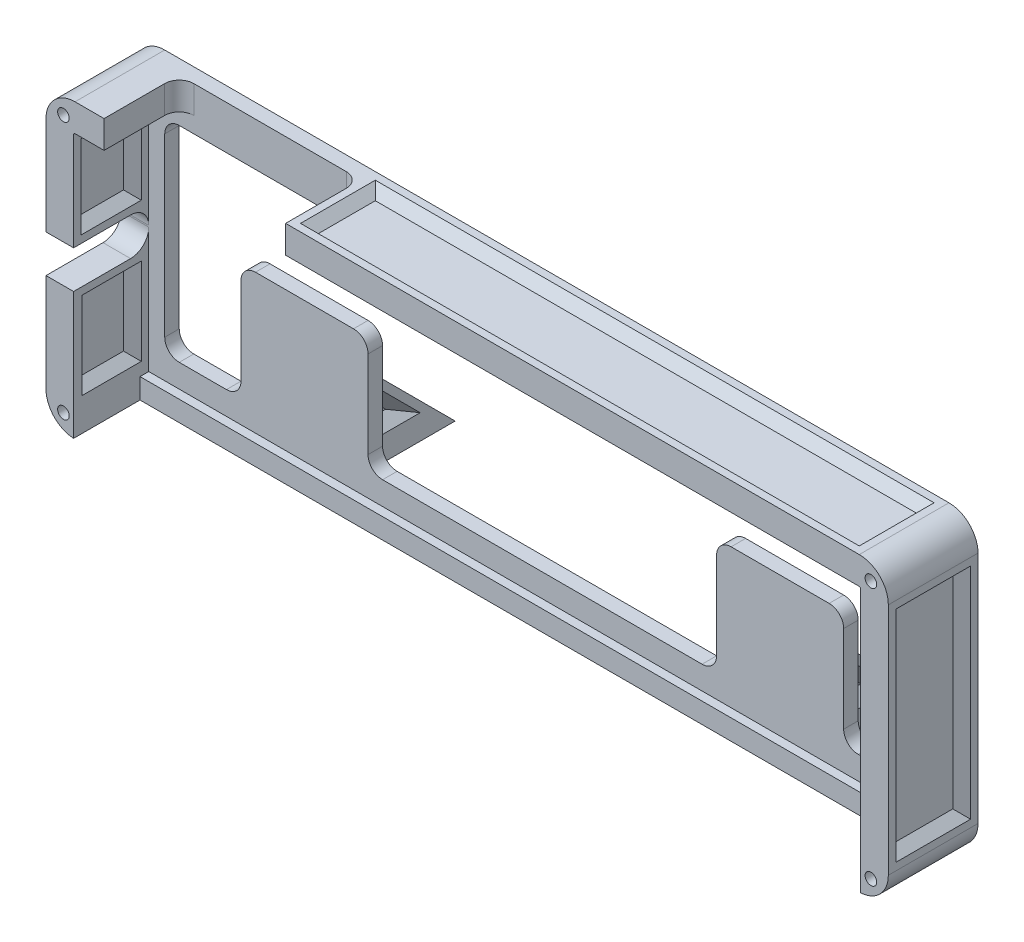
SolidWorks part; units mm, degrees
material "6061-T6 (SS)"
ref_plane "Front Plane" through (0, 0, 0) normal (0, 0, 1) x (1, 0, 0)
ref_plane "Top Plane" through (0, 0, 0) normal (0, 1, 0) x (1, 0, 0)
ref_plane "Right Plane" through (0, 0, 0) normal (1, 0, 0) x (0, 0, -1)
sketch "Sketch1" plane through (0, 0, 0) normal (0, 0, 1) x (1, 0, 0)
  line L0 (58, -16.125) -> (58, 16.125)
  line L1 (-54, -16.125) -> (54, -16.125) construction
  line L2 (-54, -16.125) -> (-54, 16.125) construction
  line L3 (-54, 16.125) -> (54, 16.125) construction
  line L4 (54, -16.125) -> (54, 16.125) construction
  line L5 (-54, -16.125) -> (54, 16.125) construction
  line L6 (-54, 16.125) -> (54, -16.125) construction
  line L7 (-54, 20.125) -> (54, 20.125)
  line L8 (-58, -16.125) -> (-58, 16.125)
  line L9 (-54, -20.125) -> (54, -20.125)
  line L10 (58, -20.125) -> (58, 20.125) construction
  line L11 (-58, 20.125) -> (58, 20.125) construction
  line L12 (-58, -20.125) -> (58, -20.125) construction
  line L13 (-58, -20.125) -> (-58, 20.125) construction
  arc A0 (58, 16.125) -> (54, 20.125) centre (54, 16.125) ccw
  arc A1 (58, -16.125) -> (54, -20.125) centre (54, -16.125) cw
  arc A2 (-58, -16.125) -> (-54, -20.125) centre (-54, -16.125) ccw
  arc A3 (-54, 20.125) -> (-58, 16.125) centre (-54, 16.125) ccw
  point P0 (0, 0)
  dimension "D4" = 4
  dimension "D1" = 108
  dimension "D2" = 32.25
  dimension "D3" = 4
extrude "Boss-Extrude1" add sketch "Sketch1" along normal blind 2 contours L7 A0 L0 A1 L9 A2 L8 A3
sketch "Sketch2" plane through (0, 0, 2) normal (0, 0, 1) x (1, 0, 0)
  line L0 (-50, 20.125) -> (-50, 16.325)
  line L1 (-25, 20.125) -> (-25, 16.325)
  line L4 (-58, 16.125) -> (-58, -16.125)
  line L5 (-54, -20.125) -> (54, -20.125)
  line L6 (58, -16.125) -> (58, 16.125)
  line L7 (54, 20.125) -> (-54, 20.125)
  line L8 (-58, 16.125) -> (-58, -16.125)
  line L9 (-54, -20.125) -> (54, -20.125)
  line L10 (58, -16.125) -> (58, 16.125)
  line L11 (54, 20.125) -> (-54, 20.125)
  line L12 (-58, 2.6) -> (-54.2, 2.6)
  line L13 (-58, -2.6) -> (-54.2, -2.6)
  line L14 (54.2, -16.125) -> (54.2, -20.12)
  line L15 (-54.2, -16.125) -> (-54.2, -20.12)
  line L16 (-54.2, 16.125) -> (-54.2, -16.125)
  line L17 (-54, -16.325) -> (54, -16.325)
  line L18 (54.2, -16.125) -> (54.2, 16.125)
  line L19 (54, 16.325) -> (-54, 16.325)
  line L20 (-54.2, 16.125) -> (-54.2, -16.125)
  line L21 (-54, -16.325) -> (54, -16.325)
  line L22 (54.2, -16.125) -> (54.2, 16.125)
  line L23 (54, 16.325) -> (-54, 16.325)
  arc A4 (-54, 20.125) -> (-58, 16.125) centre (-54, 16.125) ccw
  arc A5 (-58, -16.125) -> (-54, -20.125) centre (-54, -16.125) ccw
  arc A6 (54, -20.125) -> (58, -16.125) centre (54, -16.125) ccw
  arc A7 (58, 16.125) -> (54, 20.125) centre (54, 16.125) ccw
  arc A8 (-54, 20.125) -> (-58, 16.125) centre (-54, 16.125) ccw
  arc A9 (-58, -16.125) -> (-54, -20.125) centre (-54, -16.125) ccw
  arc A10 (54, -20.125) -> (58, -16.125) centre (54, -16.125) ccw
  arc A11 (58, 16.125) -> (54, 20.125) centre (54, 16.125) ccw
  arc A16 (-54, 16.325) -> (-54.2, 16.125) centre (-54, 16.125) ccw
  arc A17 (-54, 16.325) -> (-54.2, 16.125) centre (-54, 16.125) ccw
  arc A18 (-54.2, -16.125) -> (-54, -16.325) centre (-54, -16.125) ccw
  arc A19 (-54.2, -16.125) -> (-54, -16.325) centre (-54, -16.125) ccw
  arc A20 (54, -16.325) -> (54.2, -16.125) centre (54, -16.125) ccw
  arc A21 (54, -16.325) -> (54.2, -16.125) centre (54, -16.125) ccw
  arc A22 (54.2, 16.125) -> (54, 16.325) centre (54, 16.125) ccw
  arc A23 (54.2, 16.125) -> (54, 16.325) centre (54, 16.125) ccw
  point P20 (-54.2, 0)
  arc M13 (-54, 20.125) -> (-58, 16.125) centre (-54, 16.125) ccw
  line M14 (-58, 16.125) -> (-58, -16.125)
  arc M15 (-58, -16.125) -> (-54, -20.125) centre (-54, -16.125) ccw
  arc M17 (54, -20.125) -> (58, -16.125) centre (54, -16.125) ccw
  line M18 (58, -16.125) -> (58, 16.125)
  arc M19 (58, 16.125) -> (54, 20.125) centre (54, 16.125) ccw
  line M20 (54, 20.125) -> (-54, 20.125)
  dimension "D3" = 5.2
  dimension "D4" = 2.6
  dimension "D5" = 8
  dimension "D6" = 33
  dimension "D1" = 0
  dimension "D2" = 3.8
extrude "Boss-Extrude2" add sketch "Sketch2" along normal blind 10.35 contours L20 L13 L15 M14 M15 | A23 L22 L14 L12 L20 A17 L23 M17 M18 M19 M20 M13 M14 | A17 L23 L0 L12 L20 M20 M13 M14 region at (-55.2493, 12.4057, 2) region at (14.5, 19.2026, 2) region at (-56.0453, -10.9348, 2)
sketch "Sketch3" plane through (0, 0, 12.35) normal (0, 0, 1) x (1, 0, 0)
  line L1 (0, 0) -> (0, 16.325) construction
  line L3 (0, 0) -> (-54.1414, 0) construction
  line L4 (53.8586, 15.9836) -> (51.1716, 13.2966) construction
  circle A0 centre (-55.6, 17.75) radius 0.8
  circle A3 centre (-55.6, -17.75) radius 0.8
  circle A4 centre (55.6, -17.75) radius 0.8
  circle A5 centre (55.6, 17.75) radius 0.8
  dimension "D1" = 1.6
  dimension "D2" = 55.6
  dimension "D3" = 17.75
extrude "Cut-Extrude1" cut sketch "Sketch3" against normal blind 10
sketch "Sketch4" plane through (0, 20.125, 0) normal (0, 1, 0) x (1, 0, 0)
  line L6 (-24, -1) -> (-24, -11.35)
  line L7 (-24, -1) -> (-24, -11.35)
  line L8 (53, -1) -> (-24, -1)
  line L10 (-24, -11.35) -> (53, -11.35)
  line L11 (53, -11.35) -> (53, -1)
  line L12 (53, -1) -> (-24, -1)
  line L14 (-24, -11.35) -> (53, -11.35)
  line L15 (53, -11.35) -> (53, -1)
  dimension "D1" = 1
ref_plane "Plane1" through (0, 18.225, 0) normal (0, 1, 0) x (1, 0, 0)
extrude "Cut-Extrude2" cut sketch "Sketch4" against normal offset from surface (1.225 mm away) 0.675 up to plane "Plane1"
sketch "Sketch5" plane through (0, 16.325, 0) normal (0, -1, 0) x (1, 0, 0)
  line L4 (-24, 11.35) -> (-24, 3)
  line L5 (-24, 11.35) -> (-24, 3)
  line L6 (-24, 3) -> (53, 3)
  line L7 (-24, 3) -> (53, 3)
  line L9 (53, 3) -> (53, 11.35)
  line L10 (53, 11.35) -> (-24, 11.35)
  line L13 (53, 3) -> (53, 11.35)
  line L14 (53, 11.35) -> (-24, 11.35)
  dimension "D1" = 1
extrude "Cut-Extrude3" cut sketch "Sketch5" against normal offset from surface (1.225 mm away) 0.675 up to plane "Plane1"
chamfer "Chamfer1" distance 1.25 angle 45 8 edges at (14.5, 18.9, 11.35) (-24, 18.9, 6.175) (14.5, 18.9, 1) (53, 18.9, 6.175) (14.5, 17.55, 11.35) (53, 17.55, 7.175) (14.5, 17.55, 3) (-24, 17.55, 7.175)
sketch "Sketch6" plane through (-58, 0, 0) normal (-1, 0, 0) x (0, 0, 1)
  line L0 (12.35, 2.6) -> (2, 2.6) construction
  line L1 (1, 15.125) -> (11.35, 15.125)
  line L2 (1, 15.125) -> (1, 3.6)
  line L3 (1, 3.6) -> (11.35, 3.6)
  line L4 (11.35, 15.125) -> (11.35, 3.6)
  line L6 (1, -15.125) -> (11.35, -15.125)
  line L7 (1, -15.125) -> (11.35, -15.125)
  line L9 (11.35, -3.6) -> (1, -3.6)
  line L10 (11.35, -3.6) -> (11.35, -15.125)
  line L11 (11.35, -15.125) -> (1, -15.125)
  line L12 (1, -3.6) -> (1, -15.125)
  line L13 (11.35, -15.125) -> (11.35, -3.6)
  line L14 (11.35, -15.125) -> (11.35, -3.6)
  line L15 (11.35, -3.6) -> (1, -3.6)
  line L16 (1, -3.6) -> (1, -15.125)
  line L17 (11.35, -3.6) -> (1, -3.6)
  line L20 (1, -3.6) -> (1, -15.125)
  dimension "D2" = 1
  dimension "D1" = 1
ref_plane "Plane2" through (-56.1, 0, 0) normal (-1, 0, 0) x (0, 0, 1)
extrude "Cut-Extrude4" cut sketch "Sketch6" against normal offset from surface (1.225 mm away) 0.675 contours L4 L1 L2 L3 | L9 L12 L7 L10 region at (-58, 9.3625, 6.175) region at (-58, -9.3625, 6.175) up to plane "Plane2"
sketch "Sketch7" plane through (-54.2, 0, 0) normal (1, 0, 0) x (0, 0, -1)
  line L4 (-3, 15.125) -> (-11.35, 15.125)
  line L5 (-3, 15.125) -> (-11.35, 15.125)
  line L6 (-11.35, 3.6) -> (-3, 3.6)
  line L7 (-11.35, 3.6) -> (-3, 3.6)
  line L8 (-3, 3.6) -> (-3, 15.125)
  line L9 (-11.35, 15.125) -> (-11.35, 3.6)
  line L10 (-11.35, 15.125) -> (-11.35, 3.6)
  line L12 (-3, 3.6) -> (-3, 15.125)
  line L16 (-11.2, -15.62) -> (-3, -15.62)
  line L24 (-3, -19.12) -> (-3, -3.6)
  line L25 (-3, -3.6) -> (-11.2, -3.6)
  line L26 (-11.2, -3.6) -> (-11.2, -19.12)
  line L27 (-11.2, -19.12) -> (-3, -19.12)
  dimension "D3" = 3.5
  dimension "D1" = 1
extrude "Cut-Extrude5" cut sketch "Sketch7" against normal offset from surface (1.225 mm away) 0.675 contours L25 L26 L16 L24 | L7 L12 L5 region at (-54.2, 9.3625, 7.175) region at (-54.2, -9.61, 7.1) up to plane "Plane2"
chamfer "Chamfer2" distance 1.25 angle 45 16 edges at (-55.425, 15.125, 7.175) (-55.425, 9.3625, 3) (-55.425, 3.6, 7.175) (-55.425, -9.61, 3) (-55.425, -15.62, 7.1) (-55.425, -9.61, 11.2) (-55.425, -3.6, 7.1) (-56.775, -15.125, 6.175) (-56.775, -3.6, 6.175) (-56.775, -9.3625, 11.35) (-56.775, -9.3625, 1) (-55.425, 9.3625, 11.35) (-56.775, 9.3625, 1) (-56.775, 15.125, 6.175) (-56.775, 9.3625, 11.35) (-56.775, 3.6, 6.175)
fillet "Fillet1" radius 2.5 2 edges at (-56.1, -2.6, 2) (-56.1, 2.6, 2)
ref_plane "Plane3" through (56.1, 0, 0) normal (1, 0, 0) x (0, 0, -1)
sketch "Sketch9" plane through (58, 0, 0) normal (1, 0, 0) x (0, 0, -1)
  line L8 (-1, -15.125) -> (-1, 15.125)
  line L9 (-1, 15.125) -> (-11.35, 15.125)
  line L10 (-11.35, 15.125) -> (-11.35, -15.125)
  line L11 (-11.35, -15.125) -> (-1, -15.125)
  line L12 (-1, -15.125) -> (-1, 15.125)
  line L13 (-1, 15.125) -> (-11.35, 15.125)
  line L14 (-11.35, 15.125) -> (-11.35, -15.125)
  line L15 (-11.35, -15.125) -> (-1, -15.125)
  dimension "D1" = 1
extrude "Cut-Extrude6" cut sketch "Sketch9" against normal offset from surface (1.225 mm away) 0.675 up to plane "Plane3"
sketch "Sketch10" plane through (54.2, 0, 0) normal (-1, 0, 0) x (0, 0, 1)
  line L4 (3, -15.595) -> (11.35, -15.595)
  line L8 (3, 15.125) -> (3, -19.12)
  line L9 (3, -19.12) -> (11.35, -19.12)
  line L10 (11.35, -19.12) -> (11.35, 15.125)
  line L11 (11.35, 15.125) -> (3, 15.125)
  line L12 (3, 15.125) -> (3, -19.12)
  line L13 (3, -19.12) -> (11.35, -19.12)
  line L14 (11.35, -19.12) -> (11.35, 15.125)
  line L15 (11.35, 15.125) -> (3, 15.125)
  dimension "D1" = 1
extrude "Cut-Extrude7" cut sketch "Sketch10" against normal offset from surface (1.225 mm away) 0.675 contours L14 L15 L12 L4 region at (54.2, -0.235, 7.175) up to plane "Plane3"
chamfer "Chamfer3" distance 1.25 angle 45 8 edges at (56.775, 0, 11.35) (56.775, 15.125, 6.175) (56.775, 0, 1) (56.775, -15.125, 6.175) (55.425, -15.595, 7.175) (55.425, -0.235, 3) (55.425, 15.125, 7.175) (55.425, -0.235, 11.35)
sketch "Sketch11" plane through (0, 0, 0) normal (1, 0, 0) x (0, 0, -1)
  line L0 (0, -20.125) -> (16, -20.125)
  line L2 (16, -20.125) -> (0, -4.125)
  line L3 (0, -16.125) -> (0, 16.125) construction
  line L4 (0, -4.125) -> (0, -20.125)
  dimension "D1" = 45
  dimension "D2" = 16
extrude "Boss-Extrude3" add sketch "Sketch11" along normal blind 5.5 from offset 30
sketch "Sketch12" plane through (0, -20.125, 0) normal (0, -1, 0) x (1, 0, 0)
  line L0 (30, -8) -> (35.5, -8) construction
  line L1 (30, 0) -> (30, -16) construction
  line L2 (35.5, 0) -> (35.5, -16) construction
  circle A0 centre (32.75, -8) radius 1.8
  dimension "D1" = 3.6
extrude "Cut-Extrude8" cut sketch "Sketch12" against normal blind 3.1 draft 8
ref_plane "Plane4" through (32.75, 0, 0) normal (-1, 0, 0) x (0, 0, 1)
sketch "Sketch13" plane through (32.75, 0, 0) normal (-1, 0, 0) x (0, 0, 1)
  line L0 (-1, -6.5392) -> (-11.1858, -16.725)
  line L1 (-8, -20.125) -> (-8, -16.725) construction
  line L3 (-11.1858, -16.725) -> (-4.8, -16.725)
  line L4 (-4.8, -16.725) -> (-4.8, -19.125)
  line L5 (-4.8, -19.125) -> (-1, -19.125)
  line L6 (-1, -19.125) -> (-1, -6.5392)
  line L7 (-16, -20.125) -> (0, -4.125) construction
  line L8 (0, -4.125) -> (0, -20.125) construction
  line L9 (0, -20.125) -> (-16, -20.125) construction
  line L10 (0, -20.125) -> (-16, -20.125) construction
  dimension "D1" = 1
  dimension "D2" = 1
  dimension "D3" = 1
  dimension "D4" = 3.2
  dimension "D6" = 3.4
extrude "Cut-Extrude9" cut sketch "Sketch13" against normal up to next from offset 1.35 offset against normal yes
mirror "Mirror2" about plane through (32.75, 0, 0) normal (-1, 0, 0) of "Cut-Extrude9"
chamfer "Chamfer7" distance 1.4 angle 45 10 edges at (31.4, -19.125, -2.9) (31.4, -17.925, -4.8) (31.4, -16.725, -7.9929) (31.4, -11.6321, -6.0929) (31.4, -12.8321, -1) (34.1, -11.6321, -6.0929) (34.1, -16.725, -7.9929) (34.1, -17.925, -4.8) (34.1, -19.125, -2.9) (34.1, -12.8321, -1)
mirror "Mirror4" about plane through (0, 0, 0) normal (1, 0, 0) of "Chamfer7", "Mirror2", "Cut-Extrude9", "Cut-Extrude8", "Boss-Extrude3"
sketch "Sketch15" plane through (0, 0, 2) normal (0, 0, 1) x (1, 0, 0)
  line L0 (54.2, -20.12) -> (54.2, 16.125) construction
  line L1 (-54.2, -20.125) -> (54.2, -20.125)
  line L2 (-54.2, -20.125) -> (-54.2, -17.325)
  line L3 (-54.2, -17.325) -> (54.2, -17.325)
  line L4 (54.2, -20.125) -> (54.2, -17.325)
  line L5 (-54, -16.125) -> (54, -16.125) construction
  line L6 (-54, -20.125) -> (54, -20.125) construction
  dimension "D1" = 1.2
extrude "Boss-Extrude4" add sketch "Sketch15" along normal blind 1.2
fillet "Fillet2" radius 2 2 edges at (-50, 18.225, 2) (-25, 18.225, 2)
sketch "Sketch16" plane through (0, 0, 0) normal (0, 0, -1) x (-1, 0, 0)
  line L24 (24, 1.875) -> (41.5, 1.875)
  line L25 (41.5, 1.875) -> (41.5, -14.125)
  line L26 (41.5, -14.125) -> (52, -14.125)
  line L27 (52, -14.125) -> (52, 14.125)
  line L28 (52, 14.125) -> (-52, 14.125)
  line L29 (-52, 14.125) -> (-52, -14.125)
  line L30 (-52, -14.125) -> (-41.5, -14.125)
  line L31 (-41.5, -14.125) -> (-41.5, 1.875)
  line L32 (-41.5, 1.875) -> (-24, 1.875)
  line L33 (-24, 1.875) -> (-24, -14.125)
  line L34 (-24, -14.125) -> (24, -14.125)
  line L35 (24, -14.125) -> (24, 1.875)
  line L36 (26, 1.875) -> (39.5, 1.875)
  line L37 (41.5, -0.125) -> (41.5, -12.125)
  line L38 (43.5, -14.125) -> (50, -14.125)
  line L39 (52, -12.125) -> (52, 12.125)
  line L40 (50, 14.125) -> (-50, 14.125)
  line L41 (-52, 12.125) -> (-52, -12.125)
  line L42 (-50, -14.125) -> (-43.5, -14.125)
  line L43 (-41.5, -12.125) -> (-41.5, -0.125)
  line L44 (-39.5, 1.875) -> (-26, 1.875)
  line L45 (-24, -0.125) -> (-24, -12.125)
  line L46 (-22, -14.125) -> (22, -14.125)
  line L47 (24, -12.125) -> (24, -0.125)
  arc A4 (-50, 14.125) -> (-52, 12.125) centre (-50, 12.125) ccw
  arc A5 (52, 12.125) -> (50, 14.125) centre (50, 12.125) ccw
  arc A6 (50, -14.125) -> (52, -12.125) centre (50, -12.125) ccw
  arc A7 (41.5, -12.125) -> (43.5, -14.125) centre (43.5, -12.125) ccw
  arc A8 (39.5, 1.875) -> (41.5, -0.125) centre (39.5, -0.125) cw
  arc A9 (26, 1.875) -> (24, -0.125) centre (26, -0.125) ccw
  arc A10 (22, -14.125) -> (24, -12.125) centre (22, -12.125) ccw
  arc A11 (-24, -12.125) -> (-22, -14.125) centre (-22, -12.125) ccw
  arc A12 (-26, 1.875) -> (-24, -0.125) centre (-26, -0.125) cw
  arc A13 (-41.5, -0.125) -> (-39.5, 1.875) centre (-39.5, -0.125) cw
  arc A14 (-43.5, -14.125) -> (-41.5, -12.125) centre (-43.5, -12.125) ccw
  arc A15 (-52, -12.125) -> (-50, -14.125) centre (-50, -12.125) ccw
  dimension "D2" = 2
  dimension "D1" = 6
extrude "Cut-Extrude10" cut sketch "Sketch16" against normal up to next
